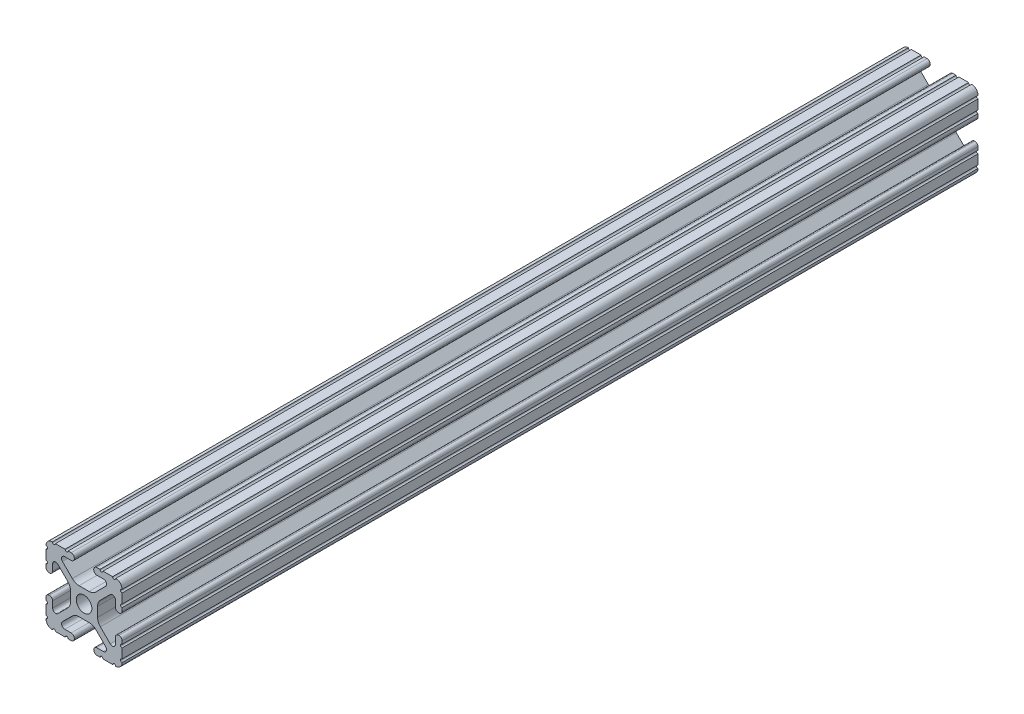
SolidWorks part; units mm, degrees
ref_plane "Front" through (0, 0, 0) normal (0, 0, 1) x (1, 0, 0)
ref_plane "Top" through (0, 0, 0) normal (0, 1, 0) x (1, 0, 0)
ref_plane "Right" through (0, 0, 0) normal (1, 0, 0) x (0, 0, -1)
sketch "Sketch1" plane through (0, 0, 0) normal (0, 0, 1) x (1, 0, 0)
  line L0 (-7.5107, 9.4563) -> (7.5107, 9.4563) construction
  line L1 (-7.4968, -9.4098) -> (7.4968, -9.4098) construction
  line L88 (-7.1797, -8.6452) -> (-3.9523, -5.4237)
  line L89 (-1.7093, -4.4958) -> (1.7093, -4.4958)
  line L90 (3.9523, -5.4237) -> (7.1797, -8.6452)
  line L91 (6.4164, -10.4902) -> (4.2875, -10.4902)
  line L92 (3.2385, -11.5392) -> (3.2385, -11.651)
  line L93 (4.2875, -12.7) -> (5.3171, -12.7)
  line L94 (6.3331, -12.7) -> (9.5504, -12.7)
  line L95 (12.7, -9.5504) -> (12.7, -6.3331)
  line L96 (12.7, -5.3171) -> (12.7, -4.2875)
  line L97 (11.651, -3.2385) -> (11.5392, -3.2385)
  line L98 (10.4902, -4.2875) -> (10.4902, -6.4021)
  line L99 (8.7371, -7.1294) -> (5.441, -3.8408)
  line L100 (4.5085, -1.5932) -> (4.5085, 1.5932)
  line L101 (5.441, 3.8408) -> (8.7371, 7.1294)
  line L102 (10.4902, 6.4021) -> (10.4902, 4.2875)
  line L103 (11.5392, 3.2385) -> (11.651, 3.2385)
  line L104 (12.7, 4.2875) -> (12.7, 5.3171)
  line L105 (12.7, 6.3331) -> (12.7, 9.5504)
  line L106 (9.5504, 12.7) -> (6.3331, 12.7)
  line L107 (5.3171, 12.7) -> (4.2875, 12.7)
  line L108 (3.2385, 11.651) -> (3.2385, 11.5392)
  line L109 (4.2875, 10.4902) -> (6.4768, 10.4902)
  line L110 (7.207, 8.7244) -> (3.8983, 5.4232)
  line L111 (1.6558, 4.4958) -> (-1.6558, 4.4958)
  line L112 (-3.8983, 5.4232) -> (-7.207, 8.7244)
  line L113 (-6.4768, 10.4902) -> (-4.2875, 10.4902)
  line L114 (-3.2385, 11.5392) -> (-3.2385, 11.651)
  line L115 (-4.2875, 12.7) -> (-5.3171, 12.7)
  line L116 (-6.3331, 12.7) -> (-9.5504, 12.7)
  line L117 (-12.7, 9.5504) -> (-12.7, 6.3331)
  line L118 (-12.7, 5.3171) -> (-12.7, 4.2875)
  line L119 (-11.651, 3.2385) -> (-11.5392, 3.2385)
  line L120 (-10.4902, 4.2875) -> (-10.4902, 6.4021)
  line L121 (-8.7371, 7.1294) -> (-5.441, 3.8408)
  line L122 (-4.5085, 1.5932) -> (-4.5085, -1.5932)
  line L123 (-5.441, -3.8408) -> (-8.7371, -7.1294)
  line L124 (-10.4902, -6.4021) -> (-10.4902, -4.2875)
  line L125 (-11.5392, -3.2385) -> (-11.651, -3.2385)
  line L126 (-12.7, -4.2875) -> (-12.7, -5.3171)
  line L127 (-12.7, -6.3331) -> (-12.7, -9.5504)
  line L128 (-9.5504, -12.7) -> (-6.3331, -12.7)
  line L129 (-5.3171, -12.7) -> (-4.2875, -12.7)
  line L130 (-3.2385, -11.651) -> (-3.2385, -11.5392)
  line L131 (-4.2875, -10.4902) -> (-6.4164, -10.4902)
  circle A1 centre (0, 0) radius 2.6035
  arc A104 (-7.1797, -8.6452) -> (-6.4164, -10.4902) centre (-6.4164, -9.4098) ccw
  arc A105 (-1.7093, -4.4958) -> (-3.9523, -5.4237) centre (-1.7093, -7.6708) ccw
  arc A106 (3.9523, -5.4237) -> (1.7093, -4.4958) centre (1.7093, -7.6708) ccw
  arc A107 (6.4164, -10.4902) -> (7.1797, -8.6452) centre (6.4164, -9.4098) ccw
  arc A108 (4.2875, -10.4902) -> (3.2385, -11.5392) centre (4.2875, -11.5392) ccw
  arc A109 (3.2385, -11.651) -> (4.2875, -12.7) centre (4.2875, -11.651) ccw
  arc A110 (6.3331, -12.7) -> (5.3171, -12.7) centre (5.8251, -12.7) ccw
  arc A111 (10.5664, -12.6998) -> (9.5504, -12.7) centre (10.0584, -12.7) ccw
  arc A112 (10.5664, -12.6998) -> (12.6998, -10.5664) centre (10.5918, -10.5918) ccw
  arc A113 (12.7, -9.5504) -> (12.6998, -10.5664) centre (12.7, -10.0584) ccw
  arc A114 (12.7, -5.3171) -> (12.7, -6.3331) centre (12.7, -5.8251) ccw
  arc A115 (12.7, -4.2875) -> (11.651, -3.2385) centre (11.651, -4.2875) ccw
  arc A116 (11.5392, -3.2385) -> (10.4902, -4.2875) centre (11.5392, -4.2875) ccw
  arc A117 (8.7371, -7.1294) -> (10.4902, -6.4021) centre (9.4628, -6.4021) ccw
  arc A118 (4.5085, -1.5932) -> (5.441, -3.8408) centre (7.6835, -1.5932) ccw
  arc A119 (5.441, 3.8408) -> (4.5085, 1.5932) centre (7.6835, 1.5932) ccw
  arc A120 (10.4902, 6.4021) -> (8.7371, 7.1294) centre (9.4628, 6.4021) ccw
  arc A121 (10.4902, 4.2875) -> (11.5392, 3.2385) centre (11.5392, 4.2875) ccw
  arc A122 (11.651, 3.2385) -> (12.7, 4.2875) centre (11.651, 4.2875) ccw
  arc A123 (12.7, 6.3331) -> (12.7, 5.3171) centre (12.7, 5.8251) ccw
  arc A124 (12.6998, 10.5664) -> (12.7, 9.5504) centre (12.7, 10.0584) ccw
  arc A125 (12.6998, 10.5664) -> (10.5664, 12.6998) centre (10.5918, 10.5918) ccw
  arc A126 (9.5504, 12.7) -> (10.5664, 12.6998) centre (10.0584, 12.7) ccw
  arc A127 (5.3171, 12.7) -> (6.3331, 12.7) centre (5.8251, 12.7) ccw
  arc A128 (4.2875, 12.7) -> (3.2385, 11.651) centre (4.2875, 11.651) ccw
  arc A129 (3.2385, 11.5392) -> (4.2875, 10.4902) centre (4.2875, 11.5392) ccw
  arc A130 (7.207, 8.7244) -> (6.4768, 10.4902) centre (6.4768, 9.4563) ccw
  arc A131 (1.6558, 4.4958) -> (3.8983, 5.4232) centre (1.6558, 7.6708) ccw
  arc A132 (-3.8983, 5.4232) -> (-1.6558, 4.4958) centre (-1.6558, 7.6708) ccw
  arc A133 (-6.4768, 10.4902) -> (-7.207, 8.7244) centre (-6.4768, 9.4563) ccw
  arc A134 (-4.2875, 10.4902) -> (-3.2385, 11.5392) centre (-4.2875, 11.5392) ccw
  arc A135 (-3.2385, 11.651) -> (-4.2875, 12.7) centre (-4.2875, 11.651) ccw
  arc A136 (-6.3331, 12.7) -> (-5.3171, 12.7) centre (-5.8251, 12.7) ccw
  arc A137 (-10.5664, 12.6998) -> (-9.5504, 12.7) centre (-10.0584, 12.7) ccw
  arc A138 (-10.5664, 12.6998) -> (-12.6998, 10.5664) centre (-10.5918, 10.5918) ccw
  arc A139 (-12.7, 9.5504) -> (-12.6998, 10.5664) centre (-12.7, 10.0584) ccw
  arc A140 (-12.7, 5.3171) -> (-12.7, 6.3331) centre (-12.7, 5.8251) ccw
  arc A141 (-12.7, 4.2875) -> (-11.651, 3.2385) centre (-11.651, 4.2875) ccw
  arc A142 (-11.5392, 3.2385) -> (-10.4902, 4.2875) centre (-11.5392, 4.2875) ccw
  arc A143 (-8.7371, 7.1294) -> (-10.4902, 6.4021) centre (-9.4628, 6.4021) ccw
  arc A144 (-4.5085, 1.5932) -> (-5.441, 3.8408) centre (-7.6835, 1.5932) ccw
  arc A145 (-5.441, -3.8408) -> (-4.5085, -1.5932) centre (-7.6835, -1.5932) ccw
  arc A146 (-10.4902, -6.4021) -> (-8.7371, -7.1294) centre (-9.4628, -6.4021) ccw
  arc A147 (-10.4902, -4.2875) -> (-11.5392, -3.2385) centre (-11.5392, -4.2875) ccw
  arc A148 (-11.651, -3.2385) -> (-12.7, -4.2875) centre (-11.651, -4.2875) ccw
  arc A149 (-12.7, -6.3331) -> (-12.7, -5.3171) centre (-12.7, -5.8251) ccw
  arc A150 (-12.6998, -10.5664) -> (-12.7, -9.5504) centre (-12.7, -10.0584) ccw
  arc A151 (-12.6998, -10.5664) -> (-10.5664, -12.6998) centre (-10.5918, -10.5918) ccw
  arc A152 (-9.5504, -12.7) -> (-10.5664, -12.6998) centre (-10.0584, -12.7) ccw
  arc A153 (-5.3171, -12.7) -> (-6.3331, -12.7) centre (-5.8251, -12.7) ccw
  arc A154 (-4.2875, -12.7) -> (-3.2385, -11.651) centre (-4.2875, -11.651) ccw
  arc A155 (-3.2385, -11.5392) -> (-4.2875, -10.4902) centre (-4.2875, -11.5392) ccw
extrude "Boss-Extrude1" add sketch "Sketch1" along normal mid plane 285.75
